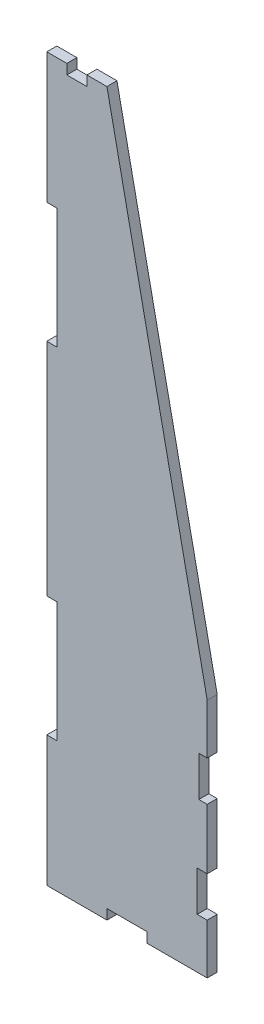
SolidWorks part; units mm, degrees
ref_plane "Front Plane" through (0, 0, 0) normal (0, 0, 1) x (1, 0, 0)
ref_plane "Top Plane" through (0, 0, 0) normal (0, 1, 0) x (1, 0, 0)
ref_plane "Right Plane" through (0, 0, 0) normal (1, 0, 0) x (0, 0, -1)
sketch "Sketch1" plane through (0, 0, 0) normal (0, 0, 1) x (1, 0, 0)
  line L0 (359.3199, 642.8699) -> (422.8199, 338.0699)
  line L1 (321.2199, 642.8699) -> (359.3199, 642.8699)
  line L2 (321.2199, 642.8699) -> (321.2199, 185.6699)
  line L3 (321.2199, 185.6699) -> (422.8199, 185.6699)
  line L4 (422.8199, 338.0699) -> (422.8199, 185.6699)
  dimension "D1" = 101.6
  dimension "D2" = 457.2
  dimension "D3" = 38.1
extrude "Boss-Extrude3" add sketch "Sketch1" along normal blind 6.35
sketch "Sketch2" plane through (0, 0, 6.35) normal (0, 0, 1) x (1, 0, 0)
  line L0 (327.5699, 642.8699) -> (327.5699, 185.6699) construction
  line L1 (359.3199, 642.8699) -> (321.2199, 642.8699) construction
  line L2 (321.2199, 185.6699) -> (422.8199, 185.6699) construction
  line L3 (321.2199, 192.0199) -> (422.8199, 192.0199) construction
  line L4 (321.2199, 642.8699) -> (321.2199, 185.6699) construction
  line L5 (422.8199, 185.6699) -> (422.8199, 338.0699) construction
  line L6 (321.2199, 636.5199) -> (360.6428, 636.5199) construction
  line L7 (416.4699, 185.6699) -> (416.4699, 368.5499) construction
  line L8 (422.8199, 338.0699) -> (359.3199, 642.8699) construction
  line L10 (346.6199, 642.8699) -> (333.9199, 642.8699)
  line L11 (346.6199, 642.8699) -> (346.6199, 636.5199)
  line L12 (346.6199, 636.5199) -> (333.9199, 636.5199)
  line L13 (333.9199, 642.8699) -> (333.9199, 636.5199)
  line L14 (321.2199, 560.3199) -> (327.5699, 560.3199)
  line L15 (321.2199, 560.3199) -> (321.2199, 484.1199)
  line L16 (321.2199, 484.1199) -> (327.5699, 484.1199)
  line L17 (327.5699, 560.3199) -> (327.5699, 484.1199)
  line L18 (321.2199, 344.4199) -> (327.5699, 344.4199)
  line L19 (321.2199, 344.4199) -> (321.2199, 268.2199)
  line L20 (321.2199, 268.2199) -> (327.5699, 268.2199)
  line L21 (327.5699, 344.4199) -> (327.5699, 268.2199)
  line L22 (359.3199, 192.0199) -> (384.7199, 192.0199)
  line L23 (359.3199, 192.0199) -> (359.3199, 185.6699)
  line L24 (359.3199, 185.6699) -> (384.7199, 185.6699)
  line L25 (384.7199, 192.0199) -> (384.7199, 185.6699)
  line L30 (416.4699, 242.8199) -> (422.8199, 242.8199)
  line L31 (416.4699, 242.8199) -> (416.4699, 217.4199)
  line L32 (416.4699, 217.4199) -> (422.8199, 217.4199)
  line L33 (422.8199, 242.8199) -> (422.8199, 217.4199)
  point P38 (419.6449, 217.4199)
  dimension "D1" = 6.35
  dimension "D2" = 6.35
  dimension "D3" = 6.35
  dimension "D4" = 6.35
  dimension "D6" = 12.7
  dimension "D8" = 82.55
  dimension "D9" = 82.55
  dimension "D10" = 25.4
  dimension "D14" = 31.75
  dimension "D7" = 25.4
  dimension "D13" = 38.1
  dimension "D5" = 12.7
  dimension "D11" = 76.2
extrude "Cut-Extrude1" cut sketch "Sketch2" against normal through all
sketch "Sketch3" plane through (0, 0, 0) normal (0, 0, 1) x (1, 0, 0)
  line L0 (422.8199, 242.8199) -> (416.4699, 242.8199) construction
  line L1 (423.8623, 306.3199) -> (417.5123, 306.3199)
  line L2 (423.8623, 306.3199) -> (423.8623, 280.9199)
  line L3 (423.8623, 280.9199) -> (417.5123, 280.9199)
  line L4 (417.5123, 306.3199) -> (417.5123, 280.9199)
  dimension "D3" = 6.35
  dimension "D2" = 38.1
extrude "Cut-Extrude2" cut sketch "Sketch3" along normal through all
equation "\"width\"= 3.5in"
equation "\"Height\"= 18in"
equation "\"D3@Sketch1\"=1.5"
equation "\"D4@Sketch1\"=\"Height\"/3"
equation "\"thick\"= 0.25"
equation "\"D1@Sketch2\"=\"thick\""
equation "\"D2@Sketch2\"=\"thick\""
equation "\"D3@Sketch2\"=\"thick\""
equation "\"D4@Sketch2\"=\"thick\""
equation "\"D2@Sketch1\"=\"Height\""
equation "\"D1@Sketch1\"=\"width\" + (\"thick\"*2)"
equation "\"D1@Boss-Extrude3\"=\"thick\""
equation "\"D3@Sketch3\"=\"thick\""
equation "\"D1@Cut-Extrude2\"=\"thick\""
